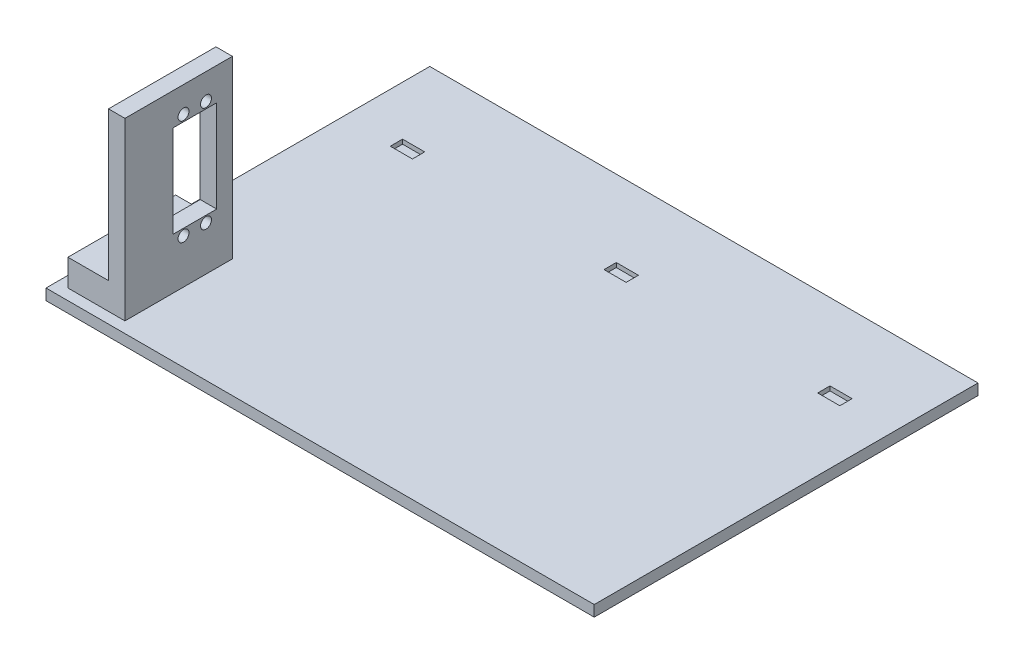
SolidWorks part; units mm, degrees
ref_plane "Front Plane" through (0, 0, 0) normal (0, 0, 1) x (1, 0, 0)
ref_plane "Top Plane" through (0, 0, 0) normal (0, 1, 0) x (1, 0, 0)
ref_plane "Right Plane" through (0, 0, 0) normal (1, 0, 0) x (0, 0, -1)
sketch "Sketch1" plane through (0, 0, 0) normal (0, 1, 0) x (1, 0, 0)
  line L0 (250, 0) -> (0, 0) construction
  line L1 (0, 0) -> (-250, 0) construction
  line L2 (-125, -87.5) -> (125, -87.5)
  line L3 (-125, -87.5) -> (-125, 87.5)
  line L4 (125, -87.5) -> (125, 87.5)
  line L5 (-125, 87.5) -> (125, 87.5)
  line L6 (-125, -87.5) -> (125, 87.5) construction
  line L7 (125, -87.5) -> (-125, 87.5) construction
  dimension "D1" = 175
  dimension "D2" = 250
extrude "Boss-Extrude1" add sketch "Sketch1" against normal blind 125
sketch "Sketch2" plane through (0, -125, 0) normal (0, -1, 0) x (1, 0, 0)
  line L0 (-125, 87.5) -> (125, 87.5) construction
  line L1 (-120, -82.5) -> (120, -82.5)
  line L2 (-120, -82.5) -> (-120, 82.5)
  line L3 (-120, 82.5) -> (120, 82.5)
  line L4 (120, -82.5) -> (120, 82.5)
  line L5 (-120, -82.5) -> (120, 82.5) construction
  line L6 (-120, 82.5) -> (120, -82.5) construction
  line L7 (125, 87.5) -> (125, -87.5) construction
  point P0 (0, 0)
  dimension "D1" = 5
  dimension "D2" = 5
extrude "Cut-Extrude1" cut sketch "Sketch2" against normal offset from surface (120 mm away) 5 up to face at (0, 0, 0)
sketch "Sketch3" plane through (0, 0, 0) normal (0, 1, 0) x (1, 0, 0)
  line L0 (-125, 0) -> (125, 0) construction
  line L1 (-125, 87.5) -> (-125, -87.5) construction
  line L2 (125, -87.5) -> (125, 87.5) construction
  line L3 (0, 87.5) -> (0, -120.2082) construction
  line L4 (-20.05, -82.5) -> (20.05, -82.5)
  line L5 (-20.05, -82.5) -> (-20.05, 82.5)
  line L6 (-20.05, 82.5) -> (20.05, 82.5)
  line L7 (20.05, -82.5) -> (20.05, 82.5)
  line L8 (-20.05, -82.5) -> (20.05, 82.5) construction
  line L9 (-20.05, 82.5) -> (20.05, -82.5) construction
  line L10 (125, 87.5) -> (-125, 87.5) construction
  point P6 (0, 0)
  dimension "D1" = 40.1
  dimension "D2" = 5
extrude "Cut-Extrude2" cut sketch "Sketch3" against normal through all
sketch "Sketch4" plane through (-125, 0, 0) normal (-1, 0, 0) x (0, 0, 1)
  line L0 (0, 0) -> (0, -125) construction
  line L1 (-87.5, -125) -> (87.5, -125) construction
  circle A0 centre (0, -62.5) radius 6
  point P7 (0, -62.5)
  point P8 (0, -62.5)
  point P10 (0, -62.5)
  dimension "D1" = 62.5
  dimension "D2" = 12
sketch "Sketch6" plane through (0, -125, 0) normal (0, -1, 0) x (1, 0, 0)
  line L1 (-125, 87.5) -> (125, 87.5)
  line L2 (-125, 87.5) -> (-125, -87.5)
  line L3 (-125, -87.5) -> (125, -87.5)
  line L4 (125, 87.5) -> (125, -87.5)
extrude "Boss-Extrude2" add sketch "Sketch6" against normal blind 5
sketch "Sketch7" plane through (0, 0, -87.5) normal (0, 0, -1) x (-1, 0, 0)
  line L0 (0, 0) -> (0, -125) construction
  line L1 (-125, -125) -> (125, -125) construction
  line L3 (-102.5, -120) -> (102.5, -120)
  line L4 (-102.5, -120) -> (-102.5, -90)
  line L5 (-102.5, -90) -> (102.5, -90)
  line L6 (102.5, -120) -> (102.5, -90)
  line L7 (-102.5, -120) -> (102.5, -90) construction
  line L8 (-102.5, -90) -> (102.5, -120) construction
  point P5 (0, -105)
  dimension "D1" = 205
  dimension "D2" = 30
  dimension "D3" = 5
extrude "Piano Plug" cut sketch "Sketch7" against normal up to surface (5 mm away) up to face at (0, -32.5, -82.5)
sketch "Sketch8" plane through (0, 0, 0) normal (0, 1, 0) x (1, 0, 0)
  line L0 (125, 87.5) -> (-125, 87.5) construction
  line L1 (-25.05, 87.5) -> (24.95, 87.5)
  line L2 (-25.05, 87.5) -> (-25.05, -92.5)
  line L3 (-25.05, -92.5) -> (24.95, -92.5)
  line L4 (24.95, 87.5) -> (24.95, -92.5)
  line L5 (-20.05, 82.5) -> (-20.05, -82.5) construction
  dimension "D1" = 50
  dimension "D2" = 5
  dimension "D3" = 180
extrude "Arm Hole" cut sketch "Sketch8" against normal up to surface (120 mm away) up to face at (0, -120, -42.5)
sketch "Sketch9" plane through (-25.05, 0, 0) normal (1, 0, 0) x (0, 0, -1)
  line L0 (87.5, 0) -> (87.5, -90)
  line L13 (0, 0) -> (0, -5)
  line L14 (87.5, 0) -> (-87.5, 0) construction
  line L15 (-82.5, -5) -> (82.5, -5) construction
  line L16 (0, -5) -> (82.5, -5)
  line L17 (82.5, -5) -> (82.5, -90)
  line L18 (82.5, -90) -> (87.5, -90)
  line L19 (0, 0) -> (87.5, 0)
extrude "Boss-Extrude8" add sketch "Sketch9" along normal through all
extrude "Main Shaft Hole" cut sketch "Sketch4" against normal through all
sketch "Sketch10" plane through (-125, 0, 0) normal (-1, 0, 0) x (0, 0, 1)
  circle A0 centre (50.8, -62.5) radius 20
  dimension "D2" = 40
  dimension "D1" = 50.8
extrude "Cut-Extrude8" cut sketch "Sketch10" against normal blind 33 and the other way blind 16
sketch "Sketch11" plane through (0, -125, 0) normal (0, -1, 0) x (-1, 0, 0)
  line L0 (125, -87.5) -> (-125, -87.5) construction
  line L1 (115, -77.5) -> (-115, -77.5)
  line L2 (115, -77.5) -> (115, 77.5)
  line L3 (115, 77.5) -> (-115, 77.5)
  line L4 (-115, -77.5) -> (-115, 77.5)
  line L5 (125, 87.5) -> (125, -87.5) construction
  line L6 (-125, 87.5) -> (125, 87.5) construction
  line L7 (-125, -87.5) -> (-125, 87.5) construction
  dimension "D1" = 10
  dimension "D2" = 10
  dimension "D3" = 10
  dimension "D4" = 10
extrude "Bottom Open" cut sketch "Sketch11" against normal blind 21 and the other way blind 28
sketch "Sketch12" plane through (-115, 0, 0) normal (1, 0, 0) x (0, 0, -1)
  line L0 (77.5, -125) -> (-77.5, -125) construction
  line L1 (77.5, -120) -> (36.4665, -120)
  line L2 (77.5, -120) -> (77.5, -125)
  line L3 (77.5, -125) -> (36.4665, -125)
  line L4 (36.4665, -120) -> (36.4665, -125)
extrude "Boss-Extrude4" add sketch "Sketch12" along normal blind 233
sketch "Sketch13" plane through (0, 0, 82.5) normal (0, 0, -1) x (-1, 0, 0)
  line L0 (120, -120) -> (25.05, -120) construction
  line L1 (101.5, -120) -> (94, -120)
  line L2 (101.5, -120) -> (101.5, -40)
  line L3 (101.5, -40) -> (94, -40)
  line L4 (94, -120) -> (94, -40)
  line L5 (120, -5) -> (120, -120) construction
  dimension "D1" = 7.5
  dimension "D2" = 18.5
  dimension "D3" = 80
extrude "Boss-Extrude5" add sketch "Sketch13" along normal blind 49
sketch "Sketch14" plane through (-115, 0, 0) normal (1, 0, 0) x (0, 0, -1)
  line L0 (-77.5, -125) -> (36.4665, -125) construction
  line L1 (-77.5, -120) -> (-33.3868, -120)
  line L2 (-77.5, -120) -> (-77.5, -125)
  line L3 (-77.5, -125) -> (-33.3868, -125)
  line L4 (-33.3868, -120) -> (-33.3868, -125)
extrude "Boss-Extrude6" add sketch "Sketch14" along normal blind 21
fillet "Fillet2" radius 5 1 edges at (-97.75, -120, 33.5)
sketch "Sketch16" plane through (0, 0, 0) normal (1, 0, 0) x (0, 0, -1)
  line L1 (-60.6684, -48.7422) -> (-40.6684, -48.7422)
  line L2 (-60.6684, -48.7422) -> (-60.6684, -102.7422)
  line L3 (-60.6684, -102.7422) -> (-40.6684, -102.7422)
  line L4 (-40.6684, -48.7422) -> (-40.6684, -102.7422)
  line L5 (-60.6684, -102.7422) -> (-40.6684, -102.7422)
  line L6 (-60.6684, -102.7422) -> (-60.6684, -96.7422)
  line L7 (-60.6684, -96.7422) -> (-40.6684, -96.7422)
  line L8 (-40.6684, -102.7422) -> (-40.6684, -96.7422)
  line L9 (-60.6684, -48.7422) -> (-40.6684, -48.7422)
  line L10 (-60.6684, -48.7422) -> (-60.6684, -54.7422)
  line L11 (-60.6684, -54.7422) -> (-40.6684, -54.7422)
  line L12 (-40.6684, -48.7422) -> (-40.6684, -54.7422)
  circle A0 centre (-55.7934, -51.7422) radius 2.5
  circle A1 centre (-45.5434, -51.7422) radius 2.5
  circle A2 centre (-55.7934, -99.7422) radius 2.5
  circle A3 centre (-45.5434, -99.7422) radius 2.5
  dimension "D3" = 5
  dimension "D6" = 5
  dimension "D8" = 5
  dimension "D11" = 5
  dimension "D1" = 20
  dimension "D2" = 54
  dimension "D4" = 3
  dimension "D5" = 4.875
  dimension "D7" = 4.875
  dimension "D9" = 3
  dimension "D10" = 4.875
  dimension "D12" = 6
  dimension "D13" = 6
extrude "Servo Plug Hole" cut sketch "Sketch16" against normal blind 106 contours A1 | A0 | L11 L2 L7 L4 | A3 | A2 region at (0, -75.7422, 50.6684) region at (0, -51.7422, 55.7934) region at (0, -51.7422, 45.5434) region at (0, -99.7422, 55.7934) region at (0, -99.7422, 45.5434)
sketch "Sketch17" plane through (-101.5, 0, 0) normal (-1, 0, 0) x (0, 0, 1)
  line L0 (82.5, -120) -> (82.5, -40) construction
  line L1 (33.3868, -120) -> (82.5, -120)
  line L2 (33.3868, -120) -> (33.3868, -107.8359)
  line L3 (33.3868, -107.8359) -> (82.5, -107.8359)
  line L4 (82.5, -120) -> (82.5, -107.8359)
extrude "Boss-Extrude7" add sketch "Sketch17" along normal blind 23
sketch "Sketch19" plane through (0, -120, 0) normal (0, 1, 0) x (1, 0, 0)
  line L0 (-120, 52.6) -> (120, 52.6) construction
  line L1 (-120, 82.5) -> (-120, -82.5) construction
  line L2 (120, -82.5) -> (120, 82.5) construction
  line L3 (102.5, 87.5) -> (102.5, 36.4665) construction
  line L4 (-102.5, 87.5) -> (-102.5, 36.4665) construction
  line L5 (115, 36.4665) -> (-115, 36.4665) construction
  line L6 (0, 87.5) -> (0, 36.4665) construction
  line L7 (102.5, 87.5) -> (-102.5, 87.5) construction
  line L8 (-120, 47) -> (120, 47) construction
  line L9 (-120, 82.5) -> (-120, -33.3868) construction
  line L10 (120, -82.5) -> (120, 82.5) construction
  line L12 (102.5, 47) -> (92.4, 47)
  line L13 (102.5, 47) -> (102.5, 52.6)
  line L14 (102.5, 52.6) -> (92.4, 52.6)
  line L15 (92.4, 47) -> (92.4, 52.6)
  line L16 (-102.5, 52.6) -> (-92.4, 52.6)
  line L17 (-102.5, 52.6) -> (-102.5, 47)
  line L18 (-102.5, 47) -> (-92.4, 47)
  line L19 (-92.4, 52.6) -> (-92.4, 47)
  line L20 (-5.05, 47) -> (5.05, 47)
  line L21 (-5.05, 47) -> (-5.05, 52.6)
  line L22 (-5.05, 52.6) -> (5.05, 52.6)
  line L23 (5.05, 47) -> (5.05, 52.6)
  line L24 (-5.05, 47) -> (5.05, 52.6) construction
  line L25 (-5.05, 52.6) -> (5.05, 47) construction
  point P32 (0, 49.8)
  dimension "D1" = 40.5
  dimension "D2" = 34.9
  dimension "D3" = 10.1
extrude "Cut-Extrude9" cut sketch "Sketch19" against normal blind 2
sketch "Sketch21" plane through (0, 0, -87.5) normal (0, 0, -1) x (-1, 0, 0)
  line L0 (-102.5, -120) -> (-102.5, -125) construction
  line L1 (-115, -125) -> (115, -125) construction
  line L2 (102.5, -120) -> (102.5, -125) construction
  line L3 (-125, -125) -> (125, -125) construction
  line L4 (0, -120) -> (0, -125) construction
  line L5 (-102.5, -120) -> (102.5, -120) construction
  line L6 (-102.5, -124.55) -> (102.5, -124.55) construction
  line L8 (-102.5, -124.55) -> (-92.4, -124.55)
  line L9 (-102.5, -124.55) -> (-102.5, -123.45)
  line L10 (-102.5, -123.45) -> (-92.4, -123.45)
  line L11 (-92.4, -124.55) -> (-92.4, -123.45)
  line L12 (102.5, -124.55) -> (92.4, -124.55)
  line L13 (102.5, -124.55) -> (102.5, -123.45)
  line L14 (102.5, -123.45) -> (92.4, -123.45)
  line L15 (92.4, -124.55) -> (92.4, -123.45)
  line L16 (-5.05, -123.45) -> (5.05, -123.45)
  line L17 (-5.05, -123.45) -> (-5.05, -124.55)
  line L18 (-5.05, -124.55) -> (5.05, -124.55)
  line L19 (5.05, -123.45) -> (5.05, -124.55)
  line L20 (-5.05, -123.45) -> (5.05, -124.55) construction
  line L21 (-5.05, -124.55) -> (5.05, -123.45) construction
  point P22 (0, -124)
  dimension "D1" = 0.45
  dimension "D2" = 1.1
  dimension "D3" = 10.1
extrude "Cut-Extrude10" cut sketch "Sketch21" against normal blind 10
sketch "Sketch23" plane through (0, -120, 0) normal (0, 1, 0) x (1, 0, 0)
  line L0 (115, -20.5167) -> (-115, -20.5167) construction
  line L1 (115, -77.5) -> (115, 36.4665) construction
  line L2 (-115, 36.4665) -> (-115, -33.3868) construction
  line L4 (-115, -77.5) -> (115, -77.5)
  line L5 (-115, -77.5) -> (-115, 36.4665)
  line L6 (-115, 36.4665) -> (115, 36.4665)
  line L7 (115, -77.5) -> (115, 36.4665)
  line L8 (-115, -77.5) -> (115, 36.4665) construction
  line L9 (-115, 36.4665) -> (115, -77.5) construction
  point P6 (0, -20.5167)
extrude "Make it Panel1" add sketch "Sketch23" against normal up to surface (5 mm away) up to face at (-31.3333, -125, 24.8068)
sketch "Sketch22" plane through (0, -120, 0) normal (0, 1, 0) x (1, 0, 0)
  line L1 (-125, -87.5) -> (125, -87.5)
  line L2 (-125, -87.5) -> (-125, 87.5)
  line L3 (-125, 87.5) -> (125, 87.5)
  line L4 (125, -87.5) -> (125, 87.5)
  line L5 (-125, -87.5) -> (125, 87.5) construction
  line L6 (-125, 87.5) -> (125, -87.5) construction
  line L7 (-120, -82.5) -> (120, -82.5)
  line L8 (-120, -82.5) -> (-120, 82.5)
  line L9 (-120, 82.5) -> (120, 82.5)
  line L10 (120, -82.5) -> (120, 82.5)
  line L11 (-120, -82.5) -> (120, 82.5) construction
  line L12 (-120, 82.5) -> (120, -82.5) construction
  point P0 (0, 0)
  point P7 (0, 0)
extrude "Make it Panel3" cut sketch "Sketch22" along normal up to surface (120 mm away) up to face at (-0.025, 0, 21.875)
sketch "Sketch24" plane through (0, 0, 0) normal (0, 1, 0) x (1, 0, 0)
  line L1 (-120, -82.5) -> (120, -82.5)
  line L2 (-120, -82.5) -> (-120, 82.5)
  line L3 (-120, 82.5) -> (120, 82.5)
  line L4 (120, -82.5) -> (120, 82.5)
  line L5 (-120, -82.5) -> (120, 82.5) construction
  line L6 (-120, 82.5) -> (120, -82.5) construction
  point P0 (0, 0)
extrude "Cut-Extrude11" cut sketch "Sketch24" against normal up to surface (5 mm away) up to face at (-0.025, -5, 20.625)
sketch "Sketch25" plane through (0, -120, 0) normal (0, 1, 0) x (1, 0, 0)
  line L0 (120, 82.5) -> (123.5, 86)
  line L2 (120, 82.5) -> (120, -82.5)
  line L3 (120, -82.5) -> (-120, -82.5)
  line L4 (-120, 82.5) -> (-120, -82.5)
  line L5 (120, 82.5) -> (-120, -82.5) construction
  line L6 (120, -82.5) -> (-120, 82.5) construction
  line L7 (-123.5, -86) -> (123.5, -86)
  line L8 (-123.5, -86) -> (-123.5, 86)
  line L10 (123.5, -86) -> (123.5, 86)
  line L11 (-123.5, -86) -> (123.5, 86) construction
  line L12 (-123.5, 86) -> (123.5, -86) construction
  line L13 (-120, 82.5) -> (-123.5, 86)
  point P0 (0, 0)
  point P7 (0, 0)
  dimension "D1" = 3.5
  dimension "D2" = 3.5
extrude "Cut-Extrude12" [suppressed] cut sketch "Sketch25" against normal offset from surface (3 mm away) 2
